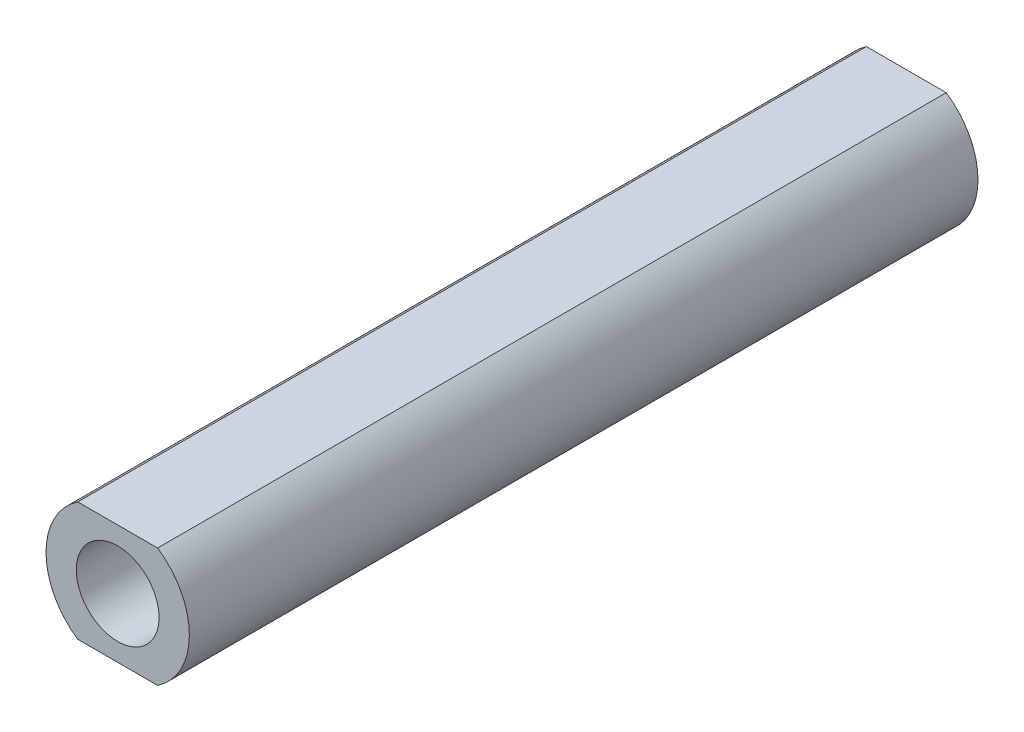
SolidWorks part; units mm, degrees
material "6061-T6 (SS)"
ref_plane "Front Plane" through (0, 0, 0) normal (0, 0, 1) x (1, 0, 0)
ref_plane "Top Plane" through (0, 0, 0) normal (0, 1, 0) x (1, 0, 0)
ref_plane "Right Plane" through (0, 0, 0) normal (1, 0, 0) x (0, 0, -1)
sketch "Sketch1" plane through (0, 0, 0) normal (0, 0, 1) x (1, 0, 0)
  line L3 (3.8592, -5.75) -> (-3.8592, -5.75)
  line L4 (0, -5.75) -> (0, 0) construction
  line L5 (0, 0) -> (4.2821, 0) construction
  line L6 (3.8592, 5.75) -> (-3.8592, 5.75)
  arc A2 (3.8592, -5.75) -> (3.8592, 5.75) centre (0, 0) ccw
  arc A3 (-3.8592, -5.75) -> (-3.8592, 5.75) centre (0, 0) cw
  dimension "D1" = 6.925
  dimension "D2" = 11.5
extrude "Boss-Extrude1" add sketch "Sketch1" along normal blind 76.2 contours A3 L3 A2 L6 region at (0, 0, 0)
hole_wizard "Ø8.0 (8) Diameter Hole1" positions "Sketch2" profile "Sketch3" hole size "Ø8.0" standard "ANSI Metric" end condition through all
sketch "Sketch2" plane through (0, 0, 0) normal (0, 0, -1) x (-1, 0, 0)
  point P0 (0, 0)
sketch "Sketch3" plane through (0, 0, 0) normal (1, 0, 0) x (0, 1, 0)
  line L0 (0, 0) -> (0, 76.2)
  line L1 (0, 76.2) -> (4, 76.2)
  line L2 (4, 76.2) -> (4, 0)
  line L5 (4, 0) -> (0, 0)
  line L11 (0, -6.35) -> (0, 107.95) construction
  dimension "Thru Hole Dia." = 8
  dimension "Thru Hole Depth" = 76.2
equation "\"D1@Sketch1\" = \"shaft diameter\" / 2"
equation "\"D2@Sketch1\" = \"shaft height\""
equation "\"shaft diameter\"= 13.85mm"
equation "\"shaft height\"= 11.5"
